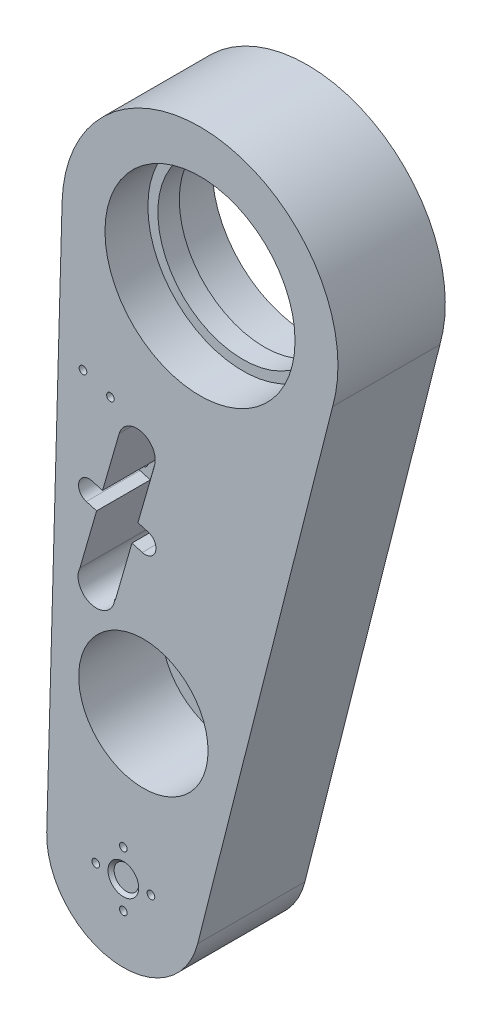
SolidWorks part; units mm, degrees
ref_plane "Ebene vorne" through (0, 0, 0) normal (0, 0, 1) x (1, 0, 0)
ref_plane "Ebene oben" through (0, 0, 0) normal (0, 1, 0) x (1, 0, 0)
ref_plane "Ebene rechts" through (0, 0, 0) normal (1, 0, 0) x (0, 0, -1)
sketch "Skizze1" plane through (0, 0, 0) normal (0, 0, 1) x (1, 0, 0)
  line L0 (-24.9904, 0.6931) -> (-19.9827, 181.2476)
  line L2 (68.9493, 170.3326) -> (24.2342, -6.1405)
  circle A0 centre (0, 0) radius 9
  circle A6 centre (0, 0) radius 25
  circle A7 centre (25, 180) radius 45
  circle A8 centre (25, 180) radius 28
  point P14 (0, 0)
  dimension "D1" = 18
  dimension "D3" = 50
  dimension "D5" = 90
  dimension "D7" = 56
  dimension "D4" = 180
  dimension "D6" = 25
extrude "Aufsatz-Linear austragen1" add sketch "Skizze1" along normal blind 35 contours A7 | A7 A6 | A6 A0 | A0 | A7 region at (11.8715, 85.5396, 0) region at (0.3368, 24.2906, 0) region at (68.6084, 168.9504, 0) region at (0, 0, 0)
sketch "Skizze2" plane through (0, 0, 35) normal (0, 0, 1) x (1, 0, 0)
  circle A0 centre (0, 0) radius 4
  dimension "D1" = 8
extrude "Schnitt-Linear austragen1" cut sketch "Skizze2" against normal blind 1 contours A0
chamfer "Fase1" distance 1 angle 45 1 edges at (4, 0, 35)
sketch "Skizze4" plane through (0, 0, 35) normal (0, 0, 1) x (1, 0, 0)
  arc A0 (-1.247, 8.9132) -> (-8.9132, 1.247) centre (0, 0) ccw
  circle A1 centre (9, 0) radius 1.25
  circle A2 centre (0, -9) radius 1.25
  circle A3 centre (-9, 0) radius 1.25
  circle A4 centre (0, 9) radius 1.25
  arc A5 (-8.9132, -1.247) -> (-1.247, -8.9132) centre (0, 0) ccw
  arc A6 (8.9132, 1.247) -> (1.247, 8.9132) centre (0, 0) ccw
  arc A7 (1.247, -8.9132) -> (8.9132, -1.247) centre (0, 0) ccw
  point P14 (0, 0)
  dimension "D1" = 18
  dimension "D2" = 4
  dimension "D3" = 2.5
extrude "Schnitt-Linear austragen2" cut sketch "Skizze4" against normal blind 15 contours A4 | A1 | A2 | A3 region at (0, 9, 35) region at (-9, 0, 35) region at (9, 0, 35) region at (0, -9, 35)
sketch "Skizze5" plane through (0, 0, 0) normal (0, 0, -1) x (-1, 0, 0)
  circle A0 centre (0, 0) radius 8
  circle A1 centre (8, 0) radius 1.25
  circle A2 centre (0, -8) radius 1.25
  circle A3 centre (-8, 0) radius 1.25
  circle A4 centre (0, 8) radius 1.25
  circle A5 centre (0, 0) radius 9.25
  point P14 (0, 0)
  dimension "D1" = 4
  dimension "D3" = 16
extrude "Schnitt-Linear austragen3" cut sketch "Skizze5" against normal blind 15 contours A0 A4 | A0 A4 | A0 A3 | A0 A3 | A0 A1 | A0 A1 | A0 A2 | A0 A2 region at (-7.4523, 0, 0) region at (-8.5125, 0, 0) region at (0, 7.4523, 0) region at (0, 8.5125, 0) region at (0, -8.5125, 0) region at (0, -7.4523, 0) region at (7.4523, 0, 0) region at (8.5125, 0, 0)
sketch "Skizze6" plane through (0, 0, 35) normal (0, 0, 1) x (1, 0, 0)
  line L1 (25, 182.9902) -> (0, 2.9902) construction
  circle A1 centre (6.5291, 50) radius 12.5
  dimension "D1" = 50
  dimension "D2" = 25
extrude "Schnitt-Linear austragen4" cut sketch "Skizze6" against normal blind 35
sketch "Skizze7" plane through (0, 0, 35) normal (0, 0, 1) x (1, 0, 0)
  circle A0 centre (6.5291, 50) radius 21.1
  dimension "D1" = 42.2
extrude "Schnitt-Linear austragen5" cut sketch "Skizze7" against normal offset from surface (27 mm away) 8 up to face at (19.0291, 50, 0)
sketch "Skizze8" plane through (0, 0, 8) normal (0, 0, 1) x (1, 0, 0)
  line L0 (6.5291, 50) -> (5.2968, 32.5434) construction
  arc A0 (5.7616, 67.4832) -> (-10.6728, 53.216) centre (6.5291, 50) ccw
  circle A1 centre (5.2968, 32.5434) radius 2
  circle A2 centre (-10.9274, 51.2323) radius 2
  circle A3 centre (7.7615, 67.4566) radius 2
  circle A4 centre (23.9857, 48.7677) radius 2
  arc A5 (24.0123, 50.7675) -> (9.7452, 67.2019) centre (6.5291, 50) ccw
  arc A6 (7.2966, 32.5168) -> (24.0123, 50.7675) centre (6.5291, 50) ccw
  arc A7 (-10.6728, 53.216) -> (3.3131, 32.7981) centre (6.5291, 50) ccw
  point P14 (6.5291, 50)
  dimension "D1" = 4
  dimension "D2" = 4
  dimension "D3" = 17.5
extrude "Schnitt-Linear austragen6" cut sketch "Skizze8" against normal blind 15 contours A4 | A3 | A1 | A2 | A2 | A4 region at (7.7615, 67.4566, 8) region at (-11.7533, 51.2906, 8) region at (23.1188, 48.8289, 8) region at (5.2968, 32.5434, 8)
sketch "Skizze9" plane through (0, 0, 0) normal (0, 0, -1) x (-1, 0, 0)
  circle A0 centre (-5.2968, 32.5434) radius 3.7
  circle A1 centre (-23.9857, 48.7677) radius 3.7
  circle A2 centre (-7.7615, 67.4566) radius 3.7
  circle A3 centre (10.9274, 51.2323) radius 3.7
  point P3 (-6.5291, 50)
  point P14 (-6.5291, 50)
  dimension "D1" = 7.4
  dimension "D2" = 4
extrude "Schnitt-Linear austragen7" cut sketch "Skizze9" against normal blind 4
sketch "Skizze10" plane through (0, 0, 35) normal (0, 0, 1) x (1, 0, 0)
  circle A0 centre (25, 180) radius 31
  dimension "D1" = 62
extrude "Schnitt-Linear austragen8" cut sketch "Skizze10" against normal blind 14
ref_plane "Ebene1" through (0, 0, 17.5) normal (0, 0, 1) x (1, 0, 0)
mirror "Spiegeln1" about plane through (0, 0, 17.5) normal (0, 0, 1) of "Schnitt-Linear austragen8"
sketch "Skizze11" plane through (0, 0, 0) normal (0, 0, 1) x (1, 0, 0)
  circle A1 centre (25.3541, 102.1802) radius 1.75
extrude "Schnitt-Linear austragen10" cut sketch "Skizze11" along normal blind 15
sketch "Skizze12" plane through (0, 0, 0) normal (0, 0, -1) x (-1, 0, 0)
  circle A1 centre (-25, 180) radius 32
  circle A4 centre (-9.1089, 136.6817) radius 2.1
  dimension "D3" = 64
extrude "Schnitt-Linear austragen11" cut sketch "Skizze12" against normal blind 20 contours A4 region at (9.1089, 136.6817, 0)
sketch "Sketch2" plane through (0, 0, 0) normal (0, 0, -1) x (-1, 0, 0)
  circle A0 centre (-4.4016, 123.4949) radius 6
extrude "Cut-Extrude1" cut sketch "Sketch2" against normal blind 35
ref_plane "Plane1" through (0, 0, 30) normal (0, 0, -1) x (-1, 0, 0)
sketch "Sketch3" plane through (0, 0, 17.5) normal (0, 0, -1) x (-1, 0, 0)
  line L0 (14.468, 79.7139) -> (1.3635, 125.1573)
  line L1 (-10.1667, 121.8324) -> (2.9378, 76.3889)
  circle A0 centre (-4.4016, 123.4949) radius 6 construction
  circle A1 centre (-4.4016, 123.4949) radius 6
  circle A2 centre (8.7029, 78.0514) radius 6
  dimension "D1" = 12
extrude "Cut-Extrude2" cut sketch "Sketch3" along normal blind 8 contours A2 L0 L1 | A2 region at (-2.1506, 100.7731, 17.5) region at (-8.7029, 78.0514, 17.5)
sketch "Sketch4" plane through (0, 0, 35) normal (0, 0, 1) x (1, 0, 0)
  circle A2 centre (-8.7869, 78.1376) radius 6
extrude "Cut-Extrude3" cut sketch "Sketch4" against normal up to surface (25.5 mm away) up to face at (-2.9819, 97.8906, 9.5)
sketch "Skizze14" plane through (0, 0, 0) normal (0, 0, -1) x (-1, 0, 0)
  circle A0 centre (-59.0996, 191.6681) radius 1.65
  circle A1 centre (4.4449, 200.7123) radius 1.655
  circle A2 centre (-26.5283, 29.0181) radius 1.65
  circle A3 centre (18.5472, 35.4337) radius 1.65
extrude "Schnitt-Linear austragen12" cut sketch "Skizze14" against normal blind 15
sketch "Skizze16" plane through (0, 0, 35) normal (0, 0, 1) x (1, 0, 0)
  circle A3 centre (-13.1725, 137.1867) radius 1.25
  circle A4 centre (-4.2165, 134.0181) radius 1.25
extrude "Schnitt-Linear austragen14" cut sketch "Skizze16" against normal blind 6
sketch "Skizze17" plane through (0, 0, 21) normal (0, 0, 1) x (1, 0, 0)
  circle A0 centre (25, 180) radius 27.75
  dimension "D1" = 55.5
extrude "Schnitt-Linear austragen15" cut sketch "Skizze17" against normal blind 10
sketch "Sketch5" plane through (0, 0, 35) normal (0, 0, 1) x (1, 0, 0)
  line L0 (-14.1424, 80.8429) -> (-1.3635, 125.1573)
  line L1 (-1.3635, 125.1573) -> (10.1667, 121.8324)
  line L2 (10.1667, 121.8324) -> (-2.6122, 77.5179)
  line L3 (10.1667, 121.8324) -> (-2.9378, 76.3889) construction
  line L4 (-7.7529, 103.0001) -> (-14.4789, 104.9397) construction
  line L5 (-14.4789, 104.9397) -> (10.5032, 97.7356) construction
  line L6 (-6.7832, 106.3631) -> (-10.1461, 107.3329)
  line L7 (-8.7227, 99.6371) -> (-12.0857, 100.6069)
  line L8 (-1.9878, 101.3376) -> (0.7272, 110.7527) construction
  line L9 (3.7772, 99.6752) -> (10.5032, 97.7356) construction
  line L10 (2.8075, 96.3122) -> (6.1704, 95.3424)
  line L11 (4.747, 103.0381) -> (8.11, 102.0684)
  line L12 (-14.1424, 80.8429) -> (-2.6122, 77.5179)
  line L13 (4.4016, 123.4949) -> (-8.8685, 77.8571) construction
  circle A0 centre (-11.1159, 103.9699) radius 3.5
  circle A1 centre (7.1402, 98.7054) radius 3.5
  circle A2 centre (-11.1159, 103.9699) radius 1.65
  circle A3 centre (7.1402, 98.7054) radius 1.65
  circle M8 centre (-8.7869, 78.1376) radius 6
  circle M9 centre (4.4016, 123.4949) radius 6
  dimension "D1" = 7
extrude "Cut-Extrude4" cut sketch "Sketch5" against normal up to surface (17.5 mm away) contours L12 L2 L0 M8 M9 | A0 A2 | A0 L7 L0 | A0 L0 L6 | L2 A1 L11 | A1 A3 | L10 A1 L2 region at (-2.1317, 100.8027, 35) region at (-9.2573, 100.6049, 35) region at (-7.751, 105.8285, 35) region at (-9.4715, 100.9928, 35) region at (3.7753, 96.8468, 35) region at (5.2816, 102.0703, 35) region at (5.4958, 101.6824, 35) up to face at (-2.3062, 94.2289, 17.5)
sketch "Sketch6" plane through (0, 0, 35) normal (0, 0, 1) x (1, 0, 0)
  circle A0 centre (-11.1159, 103.9699) radius 1.65
  circle A1 centre (7.1402, 98.7054) radius 1.65
extrude "Cut-Extrude5" cut sketch "Sketch6" against normal up to surface (25.5 mm away) up to face at (-4.6765, 93.8523, 9.5)
